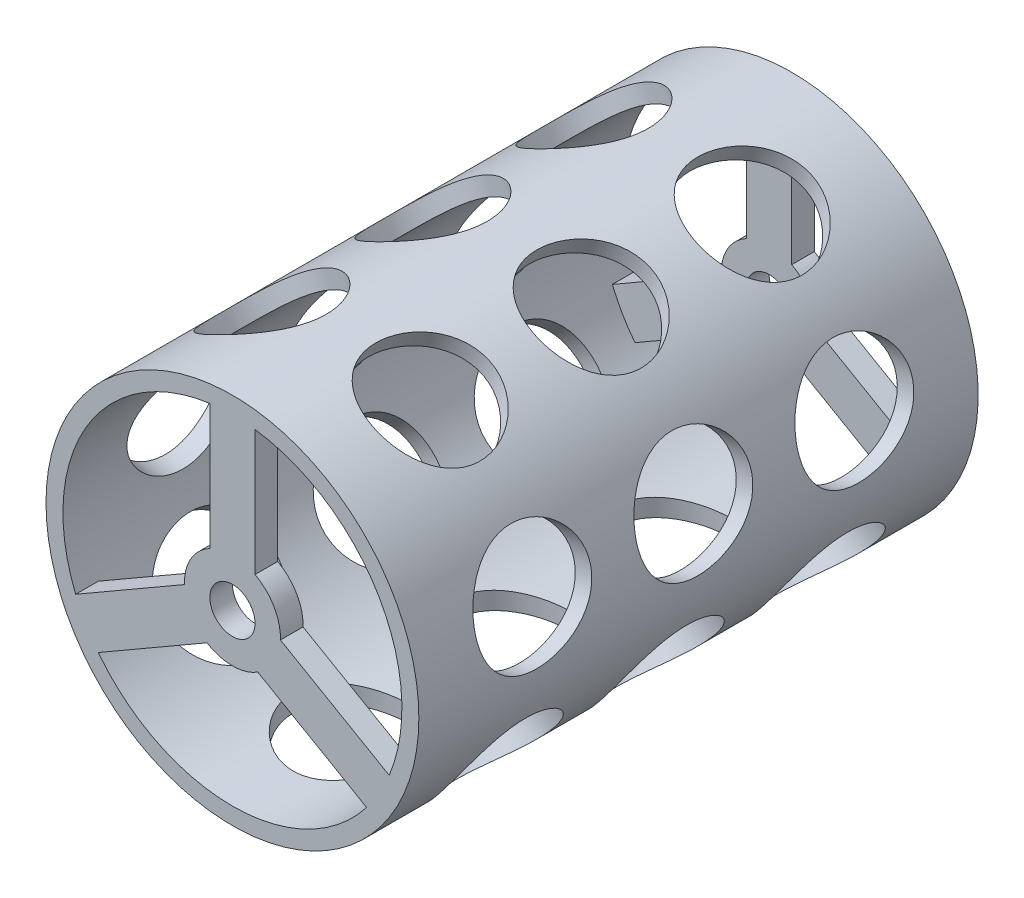
SolidWorks part; units mm, degrees
ref_plane "Ön Düzlem" through (0, 0, 0) normal (0, 0, 1) x (1, 0, 0)
ref_plane "Üst Düzlem" through (0, 0, 0) normal (0, 1, 0) x (1, 0, 0)
ref_plane "Sağ Düzlem" through (0, 0, 0) normal (1, 0, 0) x (0, 0, -1)
sketch "Çizim1" plane through (0, 0, 0) normal (0, 0, 1) x (1, 0, 0)
  circle A0 centre (0, 0) radius 30
  circle A1 centre (0, 0) radius 33
extrude "Yükseklik-Ekstrüzyon1" add sketch "Çizim1" along normal blind 95
sketch "Çizim2" plane through (0, 0, 0) normal (0, 0, -1) x (-1, 0, 0)
  circle A0 centre (0, 0) radius 33
extrude "Yükseklik-Ekstrüzyon2" add sketch "Çizim2" along normal blind 4
sketch "Çizim3" plane through (0, 0, 95) normal (0, 0, 1) x (1, 0, 0)
  circle A0 centre (0, 0) radius 33
extrude "Yükseklik-Ekstrüzyon3" add sketch "Çizim3" along normal blind 4 from offset 4 offset against normal yes
sketch "Çizim4" plane through (0, 0, -4) normal (0, 0, -1) x (-1, 0, 0)
  line L0 (8.4952, -0.2859) -> (27.7488, -11.402)
  line L1 (-4, 7.5) -> (-4, 29.7321)
  line L2 (4, 29.7321) -> (4, 7.5)
  line L3 (23.7488, -18.3302) -> (4.4952, -7.2141)
  line L4 (-4.4952, -7.2141) -> (-23.7488, -18.3302)
  line L5 (-27.7488, -11.402) -> (-8.4952, -0.2859)
  circle A0 centre (0, 0) radius 33
  arc A1 (-23.7488, -18.3302) -> (23.7488, -18.3302) centre (0, 0) ccw
  arc A2 (-4.4952, -7.2141) -> (4.4952, -7.2141) centre (0, 0) ccw
  arc A3 (-4, 7.5) -> (-8.4952, -0.2859) centre (0, 0) ccw
  arc A4 (8.4952, -0.2859) -> (4, 7.5) centre (0, 0) ccw
  arc A5 (27.7488, -11.402) -> (-27.7488, -11.402) centre (0, 0) ccw
  point P19 (0, 0)
  dimension "D1" = 3
extrude "Kes-Ekstrüzyon1" cut sketch "Çizim4" against normal blind 122 contours L1 A5 L5 A3 | L0 A5 L2 A4 | A2 L4 A1 L3 region at (-16.5918, 9.5793, -4) region at (16.5918, 9.5793, -4) region at (0, -19.1586, -4)
sketch "Çizim5" plane through (0, 0, -4) normal (0, 0, -1) x (-1, 0, 0)
  circle A0 centre (0, 0) radius 4
extrude "Kes-Ekstrüzyon2" cut sketch "Çizim5" against normal blind 122
sketch "Çizim6" plane through (0, 0, 0) normal (0, 1, 0) x (1, 0, 0)
  line L0 (33, 4) -> (-33, 4) construction
  line L1 (-33, -95) -> (33, -95) construction
  circle A0 centre (0, -17) radius 10.25
  circle A1 centre (0, -45.5) radius 10.25
  circle A2 centre (0, -74) radius 10.25
  dimension "D1" = 21
  dimension "D2" = 28.5
  dimension "D4" = 20.5
  dimension "D5" = 20.5
  dimension "D6" = 20.5
  dimension "D7" = 21
extrude "Kes-Ekstrüzyon3" cut sketch "Çizim6" against normal blind 75 and the other way blind 6
pattern_circular "Dairesel Kaplama1" count 7 over 360 about axis through (0, 0, 91) along (0, 0, 1) of "Kes-Ekstrüzyon3"
